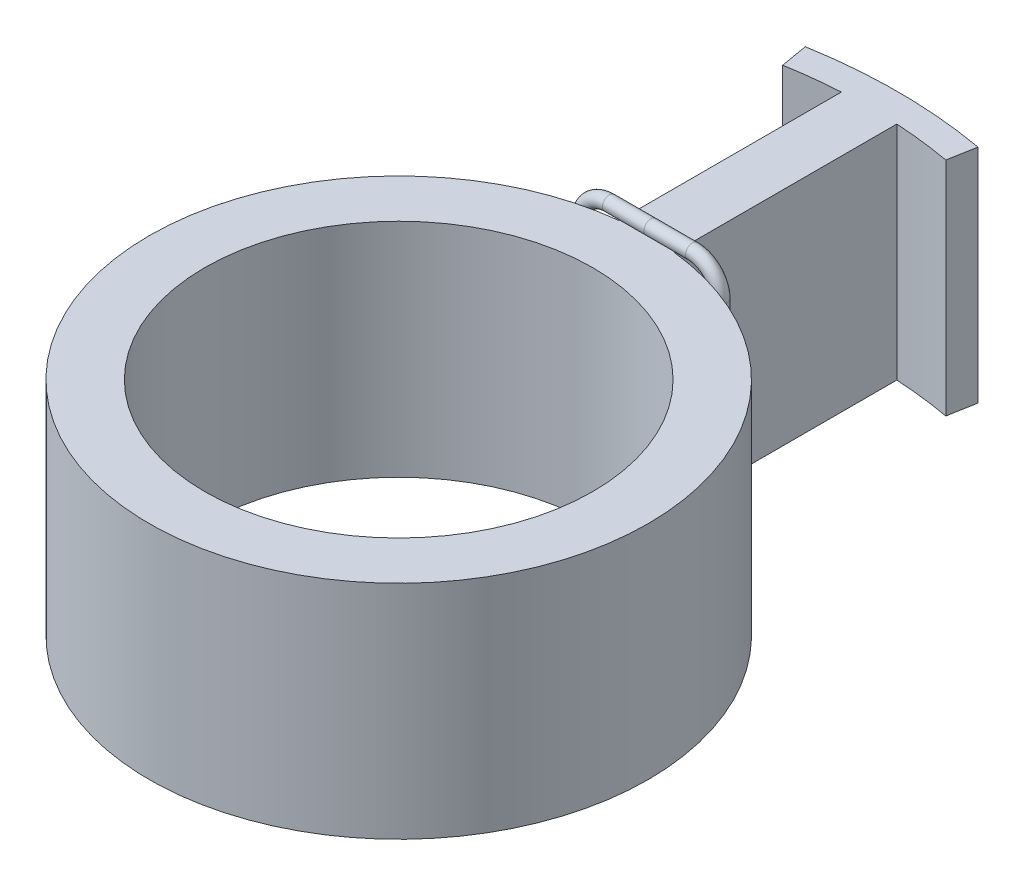
SolidWorks part; units mm, degrees
ref_plane "Front Plane" through (0, 0, 0) normal (0, 0, 1) x (1, 0, 0)
ref_plane "Top Plane" through (0, 0, 0) normal (0, 1, 0) x (1, 0, 0)
ref_plane "Right Plane" through (0, 0, 0) normal (1, 0, 0) x (0, 0, -1)
sketch "Sketch1" plane through (0, 0, 0) normal (0, 1, 0) x (1, 0, 0)
  line L0 (0, 0) -> (0, 145.9284) construction
  line L1 (-30.6747, 177.367) -> (-28.9705, 167.5133)
  line L2 (31.8383, 177.1619) -> (30.0695, 167.3195)
  line L3 (-10, 169.7056) -> (-10, 89.4427)
  line L4 (10, 169.7056) -> (10, 89.4427)
  circle A0 centre (0, 0) radius 90
  circle A1 centre (0, 0) radius 70
  arc A2 (-30.6747, 177.367) -> (31.8383, 177.1619) centre (0, 0) cw
  arc A3 (-28.9705, 167.5133) -> (-10, 169.7056) centre (0, 0) cw
  arc A4 (10, 169.7056) -> (30.0695, 167.3195) centre (0, 0) cw
  arc A5 (-28.9705, 167.5133) -> (30.0695, 167.3195) centre (0, 0) cw construction
  point P11 (-28.75, 167.2798)
  point P12 (-30.9524, 167.6639)
  point P13 (30.0695, 167.5133)
  dimension "D1" = 140
  dimension "D2" = 20
  dimension "D3" = 180
  dimension "D5" = 20
  dimension "D6" = 20
  dimension "D7" = 9.8537
  dimension "D4" = 10
extrude "Boss-Extrude1" add sketch "Sketch1" along normal blind 80 contours A0 A1 region at (0, 0, -87.4544)
extrude "Boss-Extrude2" add sketch "Sketch1<3>" along normal blind 80 contours L4 A4 L2 A2 L1 A3 L3 A0 region at (0.1578, 0, -142.0889)
sketch "Sketch1<3>" plane through (0, 0, 0) normal (0, 1, 0) x (1, 0, 0) same geometry as "Sketch1"
ref_plane "Plane1" through (0, 0, -91) normal (0, 0, 1) x (1, 0, 0)
sketch "Sketch2" plane through (0, 0, -91) normal (0, 0, 1) x (1, 0, 0)
  line L0 (0, 80) -> (0, 0) construction
  line L2 (90, 80) -> (-90, 80) construction
  line L4 (15, -2.25) -> (-15, -2.25)
  line L5 (25, 7.75) -> (25, 72.25)
  line L6 (15, 82.25) -> (-15, 82.25)
  line L7 (-25, 7.75) -> (-25, 72.25)
  line L8 (25, -2.25) -> (-25, 82.25) construction
  line L9 (25, 82.25) -> (-25, -2.25) construction
  arc A0 (-15, -2.25) -> (-25, 7.75) centre (-15, 7.75) cw
  arc A1 (25, 72.25) -> (15, 82.25) centre (15, 72.25) ccw
  arc A2 (15, -2.25) -> (25, 7.75) centre (15, 7.75) ccw
  arc A3 (-15, 82.25) -> (-25, 72.25) centre (-15, 72.25) ccw
  point P5 (0, 40)
  dimension "D3" = 10
  dimension "D1" = 50
  dimension "D2" = 84.5
sketch "Sketch3" plane through (0, 0, 0) normal (1, 0, 0) x (0, 0, -1)
  line L0 (91, 82.25) -> (91, -2.25) construction
  line L1 (91, -2.25) -> (91, 82.25) construction
  circle A0 centre (91, 82.25) radius 2.5
  dimension "D1" = 5
sweep "Sweep1" add profiles "Sketch3" path "Sketch2"
